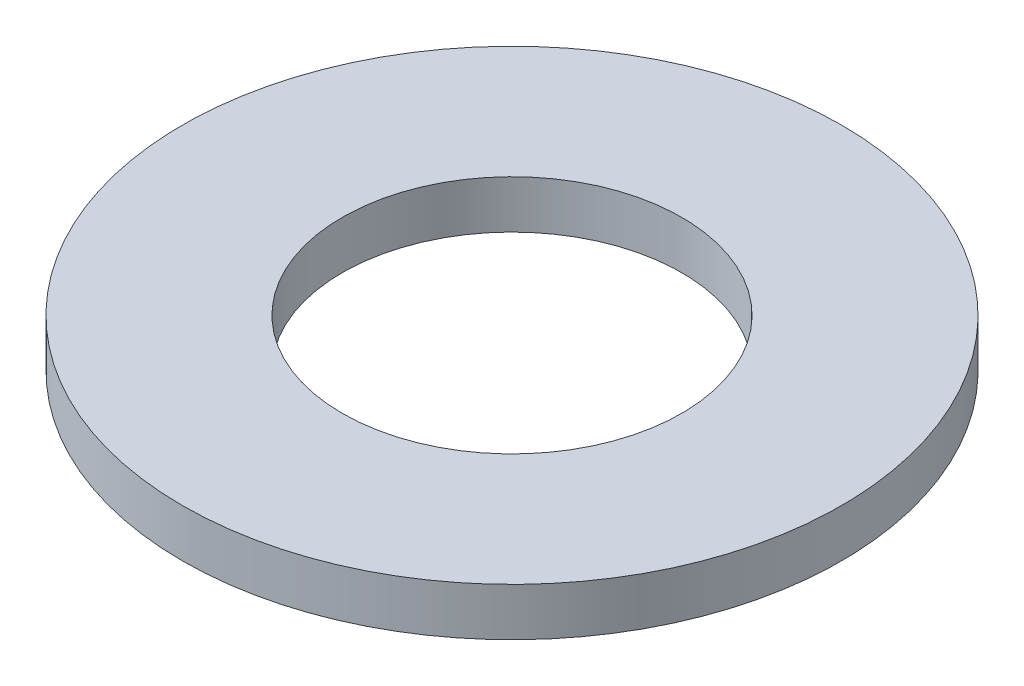
SolidWorks part; units mm, degrees
ref_plane "Front Plane" through (0, 0, 0) normal (0, 0, 1) x (1, 0, 0)
ref_plane "Top Plane" through (0, 0, 0) normal (0, 1, 0) x (1, 0, 0)
ref_plane "Right Plane" through (0, 0, 0) normal (1, 0, 0) x (0, 0, -1)
sketch "Sketch1" plane through (0, 0, 0) normal (0, 1, 0) x (1, 0, 0)
  circle A0 centre (0, 0) radius 82.5
  dimension "FLANGE_OD" = 165
extrude "Boss-Extrude1" add sketch "Sketch1" along normal blind 12
sketch "Sketch2" plane through (0, 0, 0) normal (0, 1, 0) x (1, 0, 0)
  circle A0 centre (0, 0) radius 42.5
  dimension "BORE_D" = 85
extrude "Cut-Extrude1" cut sketch "Sketch2" along normal through all
sketch "Sketch3" plane through (0, 12, 0) normal (0, 1, 0) x (1, 0, 0)
  circle A0 centre (0, 0) radius 32.932 construction
  circle A1 centre (-32.932, 0) radius 2.7769
  dimension "BOLT_D" = 5.5538
  dimension "BOLT_PCD" = 65.864
extrude "Cut-Extrude2" cut sketch "Sketch3" against normal blind 8.9068 rebuild error yes
pattern_circular "CirPattern1" count 5 over 360 rebuild error yes
